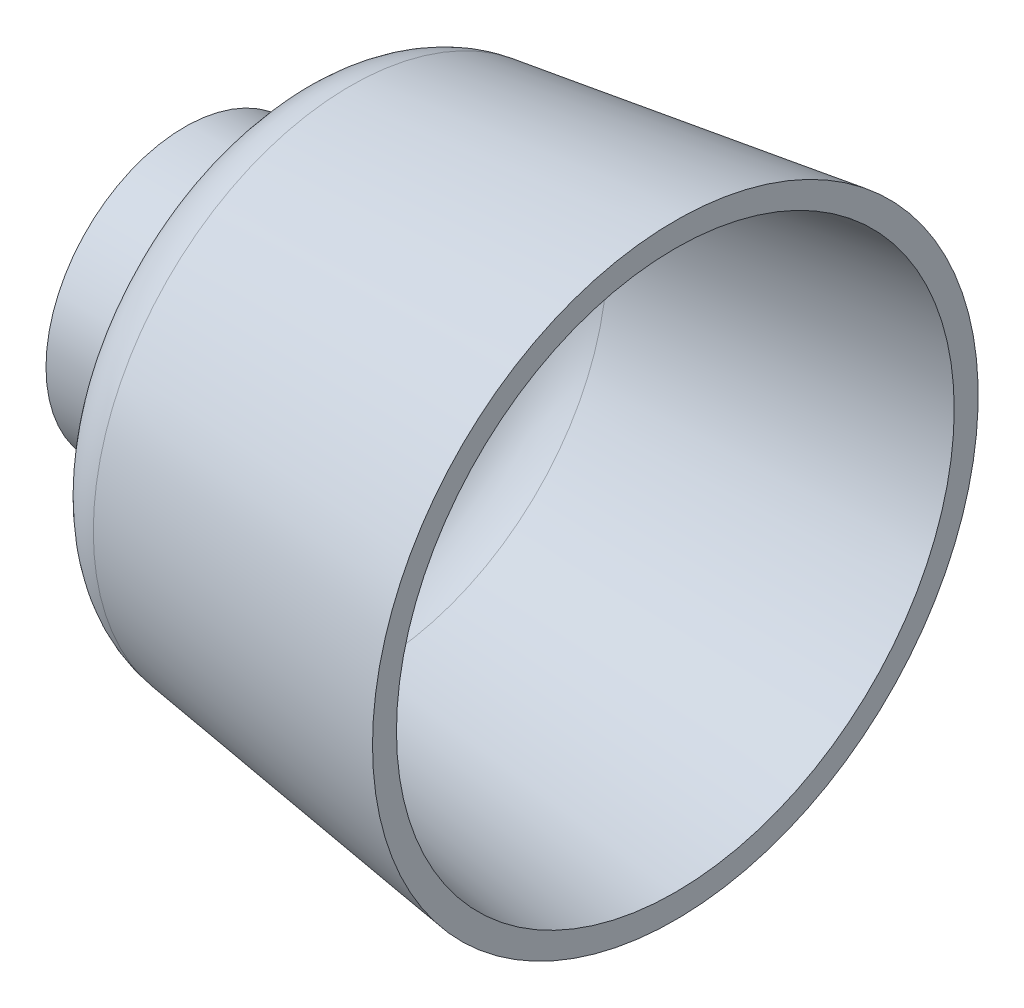
SolidWorks part; units mm, degrees
ref_plane "Front Plane" through (0, 0, 0) normal (0, 0, 1) x (1, 0, 0)
ref_plane "Top Plane" through (0, 0, 0) normal (0, 1, 0) x (1, 0, 0)
ref_plane "Right Plane" through (0, 0, 0) normal (1, 0, 0) x (0, 0, -1)
sketch "Sketch1" plane through (0, 0, 0) normal (0, 0, 1) x (1, 0, 0)
  line L0 (0, 0) -> (59.6872, 0) construction
  line L1 (0, 9.2761) -> (6.35, 9.2761)
  line L2 (6.35, 9.2761) -> (7.6626, 16.7201)
  line L3 (7.6626, 16.7201) -> (32.8154, 20.2551)
  line L4 (0, 9.2761) -> (0, 7.6886)
  line L5 (0, 7.6886) -> (7.6821, 7.6886)
  line L6 (7.6821, 7.6886) -> (9.0257, 15.3086)
  line L7 (9.0257, 15.3086) -> (32.8154, 18.652)
  line L8 (32.8154, 20.2551) -> (32.8154, 18.652)
  line L9 (0, 7.6886) -> (0, 0) construction
  dimension "D1" = 7.6886
  dimension "D2" = 6.35
  dimension "D3" = 100
  dimension "D4" = 108
  dimension "D5" = 1.5875
  dimension "D6" = 1.5875
  dimension "D7" = 1.5875
  dimension "D8" = 7.62
  dimension "D9" = 25.4
revolve "Revolve1" add sketch "Sketch1" angle 360 about L0
fillet "Fillet1" radius 4.7625 2 edges at (9.0257, 0, 15.3086) (7.6626, 0, 16.7201)
